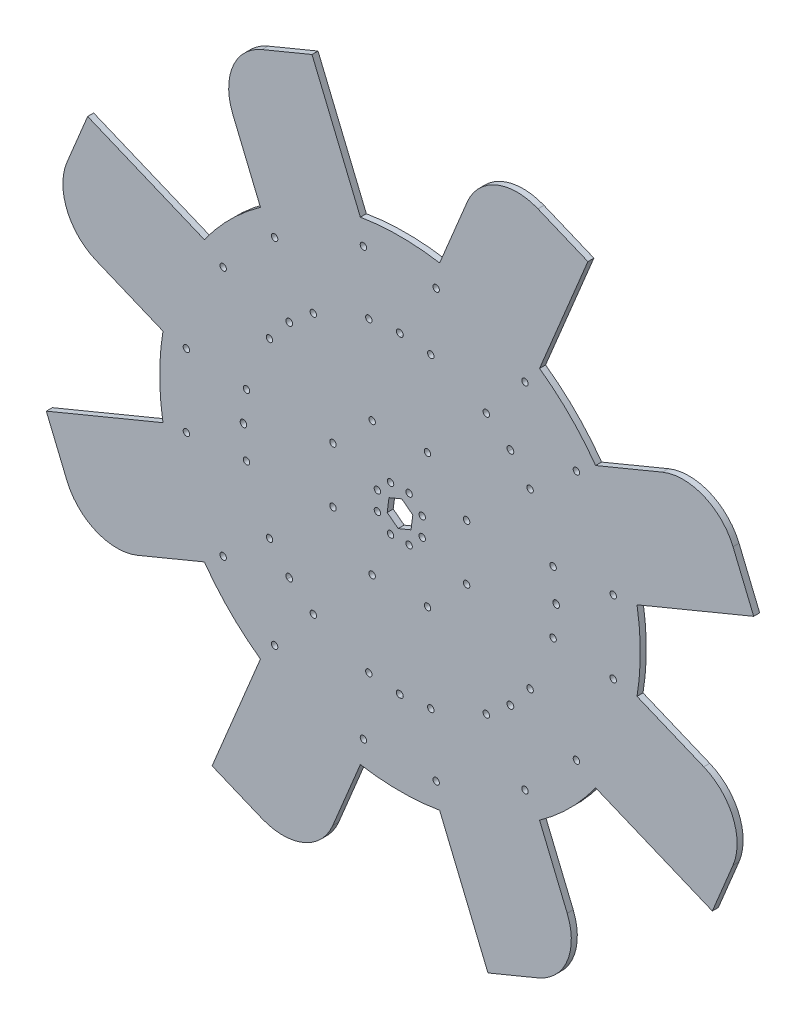
SolidWorks part; units mm, degrees
note: '?' marks a value the reader was unsure of.
ref_plane "Front Plane" through (0, 0, 0) normal (0, 0, 1) x (1, 0, 0)
ref_plane "Top Plane" through (0, 0, 0) normal (0, 1, 0) x (1, 0, 0)
ref_plane "Right Plane" through (0, 0, 0) normal (1, 0, 0) x (0, 0, -1)
sketch "Sketch1" plane through (0, 0, 0) normal (0, 0, 1) x (1, 0, 0)
  circle A0 centre (0, 0) radius 127
  dimension "D1" = 254
extrude "Boss-Extrude1" add sketch "Sketch1" along normal blind 3.175
sketch "Sketch2" plane through (0, 0, 0) normal (0, 0, 1) x (1, 0, 0)
  line L0 (0, 0) -> (117.3327, 48.6008) construction
  circle A0 centre (0, 0) radius 82.55 construction
  circle A1 centre (0, 0) radius 114.3 construction
  point P0 (11.7333, 4.8601)
  point P3 (80.9178, 16.3343)
  point P5 (58.2494, 58.4937)
  point P6 (82.5498, -0.1727)
  point P7 (112.6792, 19.1805)
  point P8 (93.2389, 66.1136)
  point P10 (68.7676, 45.6675)
  point P11 (35.1998, 14.5802)
  dimension "D1" = 12.7
  dimension "D3" = 165.1
  dimension "D4" = 228.6
  dimension "D6" = 31.75
  dimension "D2" = 63.5
  dimension "D5" = 50.8
  dimension "D7" = 38.1
hole_wizard "M3 Clearance Hole1" positions "Sketch3" profile "Sketch4" hole size "M3" standard "ANSI Metric" end condition through all
sketch "Sketch3" plane through (0, 0, 0) normal (0, 0, -1) x (-1, 0, 0)
  point P0 (-58.2494, 58.4937)
  point P3 (-82.5498, -0.1727)
  point P6 (-93.2389, 66.1136)
  point P9 (-112.6792, 19.1805)
  point P12 (-11.7333, 4.8601)
  point P16 (-68.7676, 45.6675)
  point P19 (-80.9178, 16.3343)
  point P22 (-35.1998, 14.5802)
sketch "Sketch4" plane through (58.2494, 58.4937, 0) normal (1, 0, 0) x (0, 1, 0)
  line L0 (0, 0) -> (0, 3.175)
  line L1 (0, 3.175) -> (1.7, 3.175)
  line L2 (1.7, 3.175) -> (1.7, 0)
  line L5 (1.7, 0) -> (0, 0)
  line L11 (0, -6.35) -> (0, 107.95) construction
  dimension "Thru Hole Dia." = 3.4
  dimension "Thru Hole Depth" = 3.175
ref_axis "Axis1" through (0, 0, -0.1588) along (0, 0, 1)?
pattern_circular "CirPattern1" count 8 over 360 about axis through (-0.0975, -0.0404, 0) along (0, 0, 1) of "M3 Clearance Hole1"
sketch "Sketch6" plane through (0, 0, 0) normal (0, 0, -1) x (-1, 0, 0)
  line L1 (-100.5309, 72.5706) -> (-138.664, 88.3659)
  line L2 (-175.9991, 72.9012) -> (-186.9342, 46.5013)
  line L3 (-186.9342, 46.5013) -> (-122.4012, 19.7709)
  line L4 (-122.4012, 19.7709) -> (-100.5309, 72.5706)
  line L5 (0, 0) -> (-117.3327, 48.6008) construction
  arc A0 (-175.9991, 72.9012) -> (-138.664, 88.3659) centre (-149.5992, 61.966) cw
  dimension "D5" = 28.575
  dimension "D1" = 57.15
  dimension "D3" = 190.5
  dimension "D4" = 28.575
extrude "Boss-Extrude2" add sketch "Sketch6" against normal up to surface (3.175 mm away) up to face at (-0.0975, -82.6877, 3.175)
pattern_circular "CirPattern2" count 8 over 360 about axis through (0, 0, 0) along (0, 0, 1) of "Boss-Extrude2"
sketch "Sketch8" plane through (0, 0, 0) normal (0, 0, -1) x (-1, 0, 0)
  line L1 (-6.7742, 2.806) -> (-5.8171, -4.4637)
  line L2 (-5.8171, -4.4637) -> (0.9571, -7.2696)
  line L3 (0.9571, -7.2696) -> (6.7742, -2.806)
  line L4 (6.7742, -2.806) -> (5.8171, 4.4637)
  line L5 (5.8171, 4.4637) -> (-0.9571, 7.2696)
  line L6 (-0.9571, 7.2696) -> (-6.7742, 2.806)
  circle A0 centre (0, 0) radius 6.35 construction
extrude "Cut-Extrude1" cut sketch "Sketch8" against normal up to next
